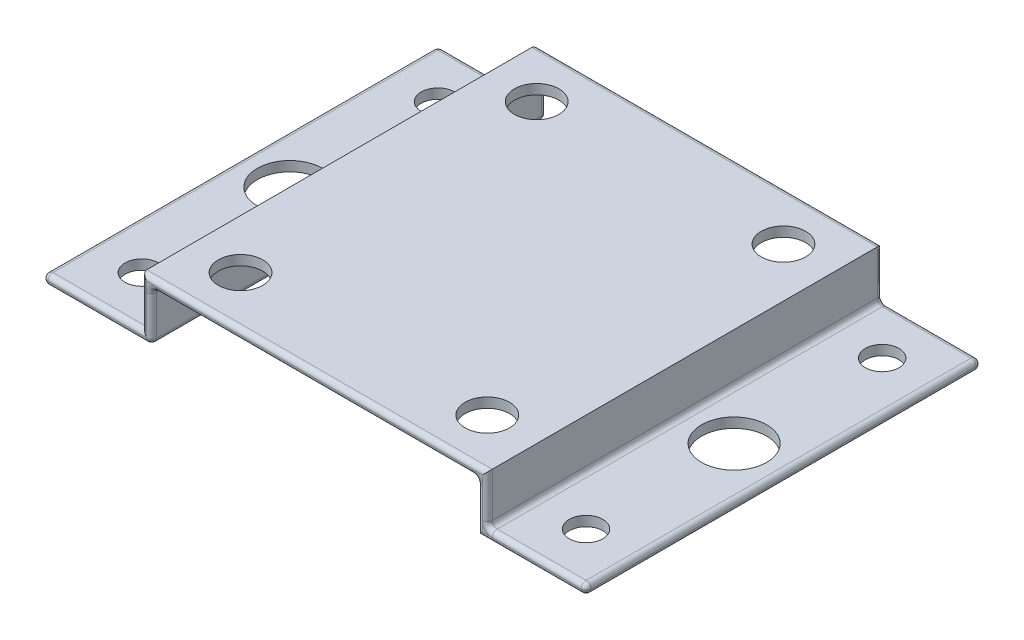
SolidWorks part; units mm, degrees
ref_plane "Front Plane" through (0, 0, 0) normal (0, 0, 1) x (1, 0, 0)
ref_plane "Top Plane" through (0, 0, 0) normal (0, 1, 0) x (1, 0, 0)
ref_plane "Right Plane" through (0, 0, 0) normal (1, 0, 0) x (0, 0, -1)
sketch "Sketch1" plane through (0, 0, 0) normal (0, 0, 1) x (1, 0, 0)
  line L0 (-17.5, 0) -> (17.5, 0)
  line L1 (17.5, 0) -> (17.5, -5)
  line L2 (17.5, -5) -> (27.5, -5)
  line L3 (-17.5, 0) -> (-17.5, -5)
  line L4 (-17.5, -5) -> (-27.5, -5)
  line L5 (-16.5, -6) -> (-27.5, -6)
  line L6 (-16.5, -1) -> (-16.5, -6)
  line L7 (-16.5, -1) -> (16.5, -1)
  line L8 (16.5, -1) -> (16.5, -6)
  line L9 (16.5, -6) -> (27.5, -6)
  line L10 (-27.5, -5) -> (-27.5, -6)
  line L11 (27.5, -5) -> (27.5, -6)
  point P4 (0, 0)
  dimension "D1" = 35
  dimension "D2" = 5
  dimension "D3" = 10
  dimension "D4" = 1
extrude "Boss-Extrude1" add sketch "Sketch1" along normal mid plane 40
fillet "Fillet1" radius 0.5 28 edges at (17.5, -2.5, -20) (0, 0, -20) (-17.5, -2.5, -20) (-22.5, -5, -20) (-22, -6, -20) (-16.5, -3.5, -20) (0, -1, -20) (16.5, -3.5, -20) (22, -6, -20) (22.5, -5, -20) (22, -6, 20) (16.5, -3.5, 20) (0, -1, 20) (-16.5, -3.5, 20) (-22, -6, 20) (-22.5, -5, 20) (-17.5, -2.5, 20) (0, 0, 20) (17.5, -2.5, 20) (22.5, -5, 20) (-27.5, -5, 0) (-27.5, -6, 0) (27.5, -6, 0) (27.5, -5, 0) (17.5, -5, 0) (-16.5, -6, 0) (-16.5, -1, 0) (16.5, -1, 0)
hole_wizard "M6 Clearance Hole1" positions "Sketch3" profile "Sketch4" hole size "M6" standard "ISO" end condition through all
sketch "Sketch3" plane through (0, -5, 0) normal (0, 1, 0) x (1, 0, 0)
  line L2 (-27.5, 19.5) -> (-27.5, -19.5) construction
  line L4 (27.5, -19.5) -> (27.5, 19.5) construction
  point P0 (-22.5, 0)
  point P2 (22.5, 0)
  point P15 (0, 0)
  dimension "D1" = 5
  dimension "D2" = 5
sketch "Sketch4" plane through (-22.5, -5, 0) normal (1, 0, 0) x (0, 0, 1)
  line L0 (0, 0) -> (0, 1)
  line L1 (0, 1) -> (3.3, 1)
  line L2 (3.3, 1) -> (3.3, 0)
  line L5 (3.3, 0) -> (0, 0)
  line L11 (0, -6.35) -> (0, 107.95) construction
  dimension "Thru Hole Dia." = 6.6
  dimension "Thru Hole Depth" = 1
hole_wizard "M4 Clearance Hole1" positions "Sketch8" profile "Sketch9" hole size "M4" standard "ISO" end condition through all
sketch "Sketch8" plane through (0, 0, 0) normal (0, 1, 0) x (1, 0, 0)
  line L0 (-17.5, -19.5) -> (-17.5, 19.5) construction
  line L1 (16, 20) -> (-16, 20) construction
  point P0 (-12.5, 15)
  dimension "D1" = 5
  dimension "D2" = 5
sketch "Sketch9" plane through (-12.5, 0, -15) normal (1, 0, 0) x (0, 0, 1)
  line L0 (0, 0) -> (0, 6)
  line L1 (0, 6) -> (2.25, 6)
  line L2 (2.25, 6) -> (2.25, 0)
  line L5 (2.25, 0) -> (0, 0)
  line L11 (0, -6.35) -> (0, 107.95) construction
  dimension "Thru Hole Dia." = 4.5
  dimension "Thru Hole Depth" = 6
hole_wizard "M3 Clearance Hole1" positions "Sketch10" profile "Sketch11" hole size "M3" standard "ISO" end condition through all
sketch "Sketch10" plane through (0, -5, 0) normal (0, 1, 0) x (1, 0, 0)
  line L0 (-27.5, 19.5) -> (-27.5, -19.5) construction
  line L1 (-17, 20) -> (-27, 20) construction
  point P0 (-22.5, 15)
  dimension "D1" = 5
  dimension "D2" = 5
sketch "Sketch11" plane through (-22.5, -5, -15) normal (1, 0, 0) x (0, 0, 1)
  line L0 (0, 0) -> (0, 1)
  line L1 (0, 1) -> (1.7, 1)
  line L2 (1.7, 1) -> (1.7, 0)
  line L5 (1.7, 0) -> (0, 0)
  line L11 (0, -6.35) -> (0, 107.95) construction
  dimension "Thru Hole Dia." = 3.4
  dimension "Thru Hole Depth" = 1
mirror "Mirror1" about plane through (0, 0, 0) normal (1, 0, 0) of "M4 Clearance Hole1", "M3 Clearance Hole1"
mirror "Mirror2" about plane through (0, 0, 0) normal (0, 0, 1) of "Mirror1", "M4 Clearance Hole1", "M3 Clearance Hole1"
